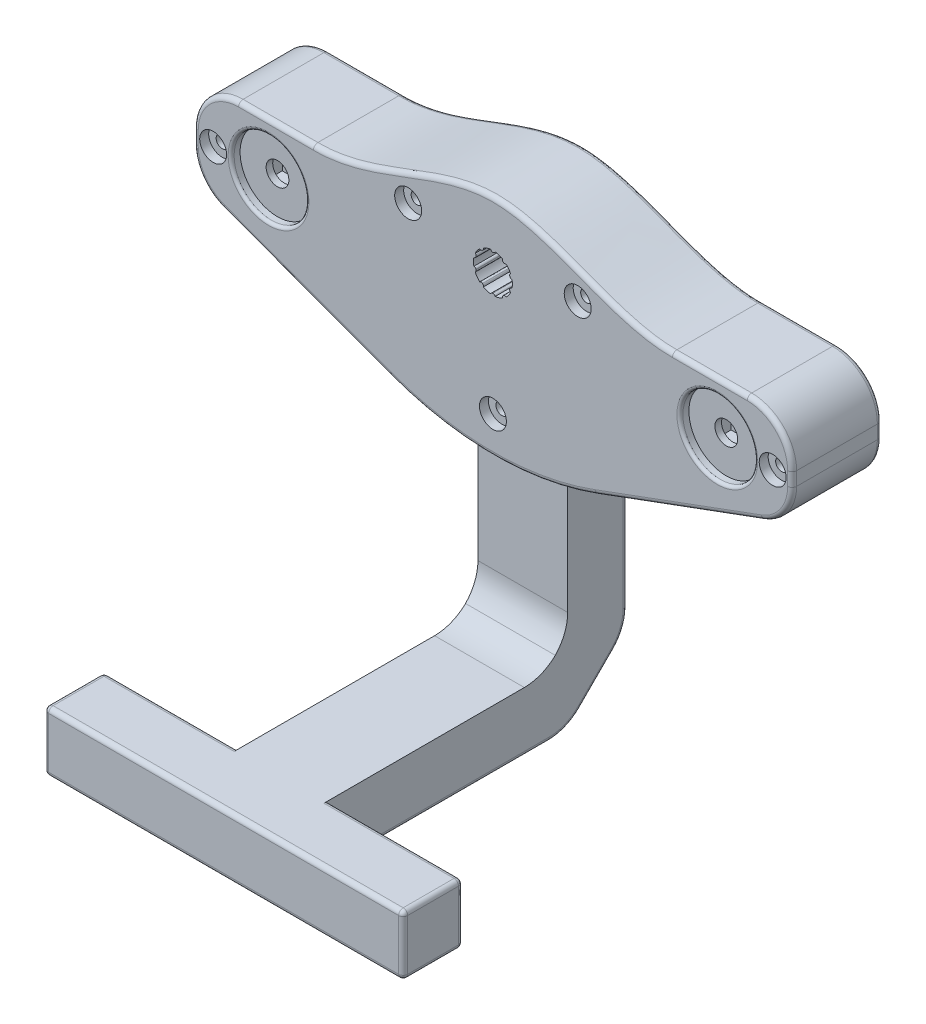
SolidWorks part; units mm, degrees
ref_plane "Front Plane" through (0, 0, 0) normal (0, 0, 1) x (1, 0, 0)
ref_plane "Top Plane" through (0, 0, 0) normal (0, 1, 0) x (1, 0, 0)
ref_plane "Right Plane" through (0, 0, 0) normal (1, 0, 0) x (0, 0, -1)
sketch "Sketch1" plane through (0, 0, 0) normal (0, 0, 1) x (1, 0, 0)
  line L0 (-100, -15) -> (0, -51.8667)
  line L2 (-100, 15) -> (-100, -15)
  line L4 (100, 15) -> (100, -15)
  line L5 (-100, 15) -> (100, -15) construction
  line L6 (-100, -15) -> (100, 15) construction
  line L7 (0, -51.8667) -> (100, -15)
  line L8 (3.1883, 2.3357) -> (2.8759, 2.7657)
  line L10 (0.75, 1.5434) -> (0.75, 2.075)
  line L11 (0.75, 2.075) -> (-0.75, 2.075)
  line L12 (-0.75, 1.5434) -> (-0.75, 2.075)
  line L13 (0, 1.5) -> (-0.75, 2.075) construction
  line L14 (0.75, 2.075) -> (0, 1.5) construction
  line L15 (4.0894, 3.6474) -> (2.8759, 2.7657)
  line L16 (4.4018, 3.2174) -> (4.0894, 3.6474)
  line L17 (5.9088, 5.2915) -> (5.4032, 5.4558)
  line L18 (5.8668, 6.8824) -> (5.4032, 5.4558)
  line L19 (6.3723, 6.7181) -> (5.8668, 6.8824)
  line L20 (6.3723, 9.2819) -> (5.8668, 9.1176)
  line L21 (5.4032, 10.5442) -> (5.8668, 9.1176)
  line L22 (5.9088, 10.7085) -> (5.4032, 10.5442)
  line L23 (4.4018, 12.7826) -> (4.0894, 12.3526)
  line L24 (2.8759, 13.2343) -> (4.0894, 12.3526)
  line L25 (3.1883, 13.6643) -> (2.8759, 13.2343)
  line L26 (0.75, 14.4566) -> (0.75, 13.925)
  line L27 (-0.75, 13.925) -> (0.75, 13.925)
  line L28 (-0.75, 14.4566) -> (-0.75, 13.925)
  line L29 (-3.1883, 13.6643) -> (-2.8759, 13.2343)
  line L30 (-4.0894, 12.3526) -> (-2.8759, 13.2343)
  line L31 (-4.4018, 12.7826) -> (-4.0894, 12.3526)
  line L32 (-5.9088, 10.7085) -> (-5.4032, 10.5442)
  line L33 (-5.8668, 9.1176) -> (-5.4032, 10.5442)
  line L34 (-6.3723, 9.2819) -> (-5.8668, 9.1176)
  line L35 (-6.3723, 6.7181) -> (-5.8668, 6.8824)
  line L36 (-5.4032, 5.4558) -> (-5.8668, 6.8824)
  line L37 (-5.9088, 5.2915) -> (-5.4032, 5.4558)
  line L38 (-4.4018, 3.2174) -> (-4.0894, 3.6474)
  line L39 (-2.8759, 2.7657) -> (-4.0894, 3.6474)
  line L40 (-3.1883, 2.3357) -> (-2.8759, 2.7657)
  line L41 (-100, 15) -> (-60, 15)
  line L42 (100, 15) -> (60, 15)
  arc A0 (0.75, 1.5434) -> (3.1883, 2.3357) centre (0, 8) ccw
  arc A1 (-3.1883, 2.3357) -> (-0.75, 1.5434) centre (0, 8) ccw
  arc A2 (-5.9088, 5.2915) -> (-4.4018, 3.2174) centre (0, 8) ccw
  arc A3 (-6.3723, 9.2819) -> (-6.3723, 6.7181) centre (0, 8) ccw
  arc A4 (-4.4018, 12.7826) -> (-5.9088, 10.7085) centre (0, 8) ccw
  arc A5 (-0.75, 14.4566) -> (-3.1883, 13.6643) centre (0, 8) ccw
  arc A6 (3.1883, 13.6643) -> (0.75, 14.4566) centre (0, 8) ccw
  arc A7 (4.4018, 3.2174) -> (5.9088, 5.2915) centre (0, 8) ccw
  arc A8 (6.3723, 6.7181) -> (6.3723, 9.2819) centre (0, 8) ccw
  arc A9 (5.9088, 10.7085) -> (4.4018, 12.7826) centre (0, 8) ccw
  spline S0 degree 3 poles (-60, 15) (-39.6994, 14.8144) (0, 45.1856) (39.6994, 14.8144) (60, 15) knots 0 0 0 0 0.5 1 1 1 1
  point P0 (0, 0)
  point P13 (0, 1.5)
  point P53 (0, 8)
  point P55 (0, 13.925)
  point P57 (0, 2.075)
  dimension "D6" = 6.5
  dimension "D2" = 40
  dimension "D3" = 40
  dimension "D4" = 30
  dimension "D5" = 30
  dimension "D7" = 11.85
  dimension "D8" = 25
  dimension "D9" = 5.5
  dimension "D10" = 5.5
  dimension "D11" = 25
  dimension "D12" = 15
  dimension "D13" = 1.5
  dimension "D14" = 22
  dimension "D1" = 10
extrude "Boss-Extrude1" add sketch "Sketch1" along normal blind 10 and the other way blind 20
sketch "Sketch18" plane through (0, 0, 0) normal (0, 0, 1) x (1, 0, 0)
  line L7 (-87.75, 12.335) -> (-62.25, 12.335)
  line L8 (-87.75, 12.335) -> (-87.75, -11.765)
  line L9 (-87.75, -11.765) -> (-62.25, -11.765)
  line L10 (-62.25, 12.335) -> (-62.25, -11.765)
  line L14 (-100, 15) -> (-60, 15) construction
  line L19 (-75, 12.335) -> (-75, -2.265) construction
  line L20 (-107.2577, -2.265) -> (-47.0612, -2.265) construction
  dimension "D1" = 24.1
  dimension "D2" = 75
  dimension "D3" = 25.5
  dimension "D6" = 14.6
  dimension "D7" = 17.265
extrude "Cut-Extrude10" cut sketch "Sketch18" along normal blind 1.1 and the other way blind 3
sketch "Sketch19" plane through (0, 0, 1.1) normal (0, 0, -1) x (-1, 0, 0)
  line L1 (70.7, 2.035) -> (79.3, 2.035)
  line L2 (70.7, 2.035) -> (70.7, -6.565)
  line L3 (70.7, -6.565) -> (79.3, -6.565)
  line L4 (79.3, 2.035) -> (79.3, -6.565)
  line L5 (70.7, 2.035) -> (79.3, -6.565) construction
  line L6 (70.7, -6.565) -> (79.3, 2.035) construction
  point P0 (75, -2.265)
  dimension "D1" = 8.6
  dimension "D2" = 8.6
sketch "Sketch20" plane through (0, 0, 1.1) normal (0, 0, -1) x (-1, 0, 0)
  line L0 (79.3, 2.035) -> (79.3, 5.335)
  line L2 (79.3, 5.335) -> (81.5, 5.335)
  line L3 (81.5, 5.335) -> (81.5, 9.835)
  line L4 (81.5, 9.835) -> (70.7, 9.835)
  line L5 (70.7, 9.835) -> (70.7, 2.035)
  line L6 (70.7, 2.035) -> (79.3, 2.035)
  line L7 (70.7, -6.565) -> (79.3, -6.565) construction
  dimension "D1" = 2.2
  dimension "D2" = 4.5
  dimension "D3" = 16.4
extrude "Cut-Extrude13" cut sketch "Sketch19" against normal blind 3.7
extrude "Cut-Extrude14" cut sketch "Sketch20" against normal blind 2
sketch "Sketch21" plane through (0, 0, 4.8) normal (0, 0, -1) x (-1, 0, 0)
  circle A0 centre (75, -2.265) radius 3.8
  dimension "D1" = 7.6
extrude "Cut-Extrude15" cut sketch "Sketch21" against normal through all
sketch "Sketch10" plane through (0, 0, 10) normal (0, 0, 1) x (1, 0, 0)
  circle A0 centre (-75, -2.265) radius 12.5
  dimension "D1" = 25
extrude "Cut-Extrude8" cut sketch "Sketch10" against normal blind 3
sketch "Sketch22" plane through (0, 0, 1.1) normal (0, 0, -1) x (-1, 0, 0)
  line L0 (62.25, -11.765) -> (62.25, 12.335) construction
  line L1 (62.25, 12.335) -> (87.75, 12.335) construction
  line L2 (87.75, 12.335) -> (87.75, -11.765) construction
  circle A0 centre (64.35, 10.235) radius 0.95
  circle A1 centre (85.65, 10.235) radius 0.95
  circle A2 centre (85.65, -2.105) radius 0.95
  circle A3 centre (64.35, -2.105) radius 0.95
  dimension "D3" = 1.9
  dimension "D6" = 1.9
  dimension "D7" = 1.9
  dimension "D9" = 1.9
  dimension "D1" = 2.1
  dimension "D2" = 2.1
  dimension "D4" = 2.1
  dimension "D5" = 2.1
  dimension "D8" = 12.34
  dimension "D10" = 2.1
  dimension "D11" = 2.1
  dimension "D12" = 12.34
extrude "Boss-Extrude5" add sketch "Sketch22" along normal blind 1.1 draft 30
ref_plane "Plane1" through (-75, 0, 0) normal (1, 0, 0) x (0, 0, -1)
sketch "Sketch24" plane through (-75, 0, 0) normal (1, 0, 0) x (0, 0, -1)
  line L0 (1.1, -11.765) -> (1.1, -19.265)
  line L1 (20, 1.5434) -> (20, 2.3357) construction
  line L3 (1.1, -19.265) -> (20, -19.265)
  line L5 (20, -19.265) -> (20, -18.665)
  line L6 (20, -18.665) -> (1.7, -18.665)
  line L8 (1.7, -18.665) -> (1.7, -11.765)
  line L9 (1.7, -11.765) -> (1.1, -11.765)
  line L12 (0, 12.335) -> (0, -11.765) construction
  point P16 (1.4, -11.765)
  dimension "D1" = 7.5
  dimension "D2" = 0.6
  dimension "D3" = 1.4
  dimension "D4" = 0.6
extrude "Cut-Extrude16" cut sketch "Sketch24" along normal mid plane 17
fillet "Fillet13" radius 2 2 edges at (-75, -18.665, -1.7) (-75, -19.265, -1.1)
sketch "Sketch25" plane through (0, 0, -3) normal (0, 0, 1) x (1, 0, 0)
  line L0 (-87.75, 12.335) -> (-87.75, -11.765) construction
  line L1 (-62.25, 12.335) -> (-87.75, 12.335) construction
  line L9 (-84.6723, 10.7392) -> (-83.3036, 10.7392)
  line L10 (-86.1542, 9.2573) -> (-86.1542, 7.8886)
  line L11 (-75, -16.0437) -> (-75, 16.0437) construction
  line L12 (-65.3277, 10.7392) -> (-66.6964, 10.7392)
  line L13 (-63.8458, 9.2573) -> (-63.8458, 7.8886)
  line L14 (-85.65, -1.005) -> (-85.65, 0.295)
  line L15 (-85.65, -3.205) -> (-85.65, -4.505)
  line L16 (-64.35, -3.205) -> (-64.35, -4.505)
  line L17 (-64.35, -1.005) -> (-64.35, 0.295)
  arc A0 (-86.1542, 9.2573) -> (-84.6723, 10.7392) centre (-85.65, 10.235) ccw
  arc A1 (-86.1542, 7.8886) -> (-83.3036, 10.7392) centre (-85.65, 10.235) ccw
  arc A4 (-85.65, -3.205) -> (-85.65, -1.005) centre (-85.65, -2.105) ccw
  arc A5 (-63.8458, 9.2573) -> (-65.3277, 10.7392) centre (-64.35, 10.235) cw
  arc A6 (-63.8458, 7.8886) -> (-66.6964, 10.7392) centre (-64.35, 10.235) cw
  arc A7 (-85.65, -4.505) -> (-85.65, 0.295) centre (-85.65, -2.105) ccw
  arc A8 (-64.35, -3.205) -> (-64.35, -1.005) centre (-64.35, -2.105) cw
  arc A9 (-64.35, -4.505) -> (-64.35, 0.295) centre (-64.35, -2.105) cw
  dimension "D3" = 2.2
  dimension "D4" = 4.8
  dimension "D6" = 2.2
  dimension "D8" = 4.8
  dimension "D1" = 2.1
  dimension "D2" = 2.1
  dimension "D5" = 2.1
  dimension "D7" = 12.34
extrude "Boss-Extrude6" add sketch "Sketch25" along normal blind 3
pattern_linear "LPattern1" count 2 spacing 150 along (1, 0, 0) of "Cut-Extrude10", "Cut-Extrude13", "Cut-Extrude14", "Cut-Extrude15", "Cut-Extrude8", "Boss-Extrude5", "Cut-Extrude16", "Fillet13", "Boss-Extrude6"
sketch "Sketch12" plane through (0, 0, -20) normal (0, 0, -1) x (-1, 0, 0)
  circle A0 centre (0, 8) radius 15
  dimension "D1" = 30
extrude "Cut-Extrude9" cut sketch "Sketch12" against normal blind 8
sketch "Sketch11" plane through (0, 0, 0) normal (0, 0, 1) x (1, 0, 0)
  line L1 (15, -46.3367) -> (-15, -46.3367)
  line L2 (15, -46.3367) -> (15, -102.265)
  line L3 (15, -102.265) -> (-15, -102.265)
  line L4 (-15, -46.3367) -> (-15, -102.265)
  line L7 (-100, -15) -> (0, -51.8667) construction
  circle A0 centre (-75, -2.265) radius 3.8 construction
  point P9 (0, -46.3367)
  dimension "D1" = 100
  dimension "D2" = 30
extrude "Boss-Extrude2" add sketch "Sketch11" against normal blind 20
sketch "Sketch16" plane through (0, 0, 0) normal (1, 0, 0) x (0, 0, -1)
  line L0 (20, -102.265) -> (0, -122.265)
  line L1 (20, -102.265) -> (20, -46.3367) construction
  line L2 (0, -122.265) -> (-100, -122.265)
  line L3 (-100, -122.265) -> (-100, -102.265)
  line L6 (-100, -102.265) -> (-8.2843, -102.265)
  line L7 (-8.2843, -102.265) -> (0, -93.9807)
  line L8 (0, -93.9807) -> (20, -102.265)
  line L10 (0, -46.3367) -> (0, -51.8667) construction
  dimension "D1" = 100
  dimension "D2" = 20
  dimension "D3" = 20
  dimension "D4" = 135
  dimension "D5" = 100
extrude "Boss-Extrude3" add sketch "Sketch16" along normal mid plane 30
sketch "Sketch17" plane through (0, -122.265, 0) normal (0, -1, 0) x (1, 0, 0)
  line L0 (15, 100) -> (-15, 100) construction
  line L1 (-60, 100) -> (60, 100)
  line L2 (-60, 100) -> (-60, 80)
  line L3 (-60, 80) -> (60, 80)
  line L4 (60, 100) -> (60, 80)
  point P4 (0, 100)
  dimension "D1" = 20
  dimension "D2" = 120
extrude "Boss-Extrude4" add sketch "Sketch17" against normal blind 20
chamfer "Chamfer1" distance 1.5 distance2 0.4624 10 edges at (-5.635, 6.1691, -12) (-3.4826, 3.2066, -12) (0, 2.075, -12) (3.4826, 3.2066, -12) (5.635, 6.1691, -12) (5.635, 9.8309, -12) (-5.635, 9.8309, -12) (-3.4826, 12.7934, -12) (0, 13.925, -12) (3.4826, 12.7934, -12)
chamfer "Chamfer2" distance 5 distance2 8 1 edges at (-15, 8, -20)
fillet "Fillet11" radius 0.78 20 edges at (-4.0894, 12.3526, -0.25) (-5.8668, 9.1176, -0.25) (-5.4032, 10.5442, -0.25) (-2.8759, 13.2343, -0.25) (-0.75, 13.925, -0.25) (0.75, 13.925, -0.25) (2.8759, 13.2343, -0.25) (4.0894, 12.3526, -0.25) (5.4032, 10.5442, -0.25) (5.8668, 9.1176, -0.25) (5.8668, 6.8824, -0.25) (5.4032, 5.4558, -0.25) (-5.8668, 6.8824, -0.25) (-5.4032, 5.4558, -0.25) (-4.0894, 3.6474, -0.25) (-2.8759, 2.7657, -0.25) (-0.75, 2.075, -0.25) (0.75, 2.075, -0.25) (2.8759, 2.7657, -0.25) (4.0894, 3.6474, -0.25)
fillet "Fillet1" radius 15 8 edges at (100, -15, -5) (-100, -15, -5) (0, -122.265, 0) (0, -102.265, -20) (0, -102.265, 8.2843) (0, -93.9807, 0) (100, 15, -5) (-100, 15, -5)
fillet "Fillet12" radius 100 1 edges at (0, -51.8667, 5)
fillet "Fillet2" radius 1.5 51 edges at (100, -2.2716, -20) (100, -2.2716, 10) (97.3051, -13.1213, -20) (97.3051, -13.1213, 10) (62.3897, -28.8657, 10) (62.3897, -28.8657, -20) (-62.3897, -28.8657, -20) (-62.3897, -28.8657, 10) (-97.3051, -13.1213, -20) (-97.3051, -13.1213, 10) (-100, -2.2716, 10) (-100, -2.2716, -20) (15, -70.1039, -20) (-15, -70.1039, -20) (15, -122.265, 43.1066) (15, -112.265, -10) (-15, -122.265, 43.1066) (-15, -112.265, -10) (15, -121.1232, 0.473) (15, -101.792, -18.8582) (-15, -121.1232, 0.473) (-15, -101.792, -18.8582) (72.5, 15, 10) (72.5, 15, -20) (95.6066, 10.6066, -20) (95.6066, 10.6066, 10) (-72.5, 15, -20) (-72.5, 15, 10) (-95.6066, 10.6066, -20) (-95.6066, 10.6066, 10) (37.5, -122.265, 80) (60, -122.265, 90) (0, -122.265, 100) (-60, -122.265, 90) (-37.5, -122.265, 80) (-60, -112.265, 80) (-60, -102.265, 90) (60, -102.265, 90) (60, -112.265, 80) (60, -112.265, 100) (-60, -112.265, 100) (0, -102.265, 100) (-37.5, -102.265, 80) (37.5, -102.265, 80) (24.9232, -42.1317, -20) (-24.9232, -42.1317, -20) (0, -45.2873, 10) (-15, -44.1559, -10) (15, -44.1559, -10)
fillet "Fillet14" radius 1 3 edges at (-62.5, -2.265, 10) (87.5, -2.265, 10) (-20, 8, -20)
sketch "Sketch32" plane through (0, 0, 10) normal (0, 0, 1) x (1, 0, 0)
  line L0 (-98.5, 0) -> (-98.5, -4.5431) construction
  line L1 (0, -70.9875) -> (0, 70.9875) construction
  circle A0 centre (-93.5, -2.2716) radius 4.5
  circle A2 centre (-28.3322, 14.0083) radius 4.5
  circle A3 centre (0, -32.7928) radius 4.5
  circle A7 centre (28.3322, 14.0083) radius 4.5
  circle A9 centre (93.5, -2.2716) radius 4.5
  point P6 (-98.5, -2.2716)
  dimension "D1" = 9
  dimension "D3" = 9
  dimension "D4" = 9
  dimension "D2" = 5
sketch "Sketch33" plane through (0, 0, 10) normal (0, 0, 1) x (1, 0, 0)
  circle A0 centre (-28.3322, 14.0083) radius 2
  circle A1 centre (-93.5, -2.2716) radius 2
  circle A2 centre (0, -32.7928) radius 2
  circle A3 centre (28.3322, 14.0083) radius 2
  circle A4 centre (93.5, -2.2716) radius 2
extrude "Cut-Extrude17" cut sketch "Sketch32" against normal blind 3
extrude "Cut-Extrude18" cut sketch "Sketch33" against normal through all
sketch "Sketch35" plane through (0, 0, -20) normal (0, 0, -1) x (-1, 0, 0)
  line L1 (-98.05, 0.3554) -> (-98.05, -4.8985)
  line L2 (-98.05, -4.8985) -> (-93.5, -7.5254)
  line L3 (-93.5, -7.5254) -> (-88.95, -4.8985)
  line L4 (-88.95, -4.8985) -> (-88.95, 0.3554)
  line L5 (-88.95, 0.3554) -> (-93.5, 2.9823)
  line L6 (-93.5, 2.9823) -> (-98.05, 0.3554)
  line L7 (4.55, -30.1659) -> (0, -27.539)
  line L8 (0, -27.539) -> (-4.55, -30.1659)
  line L9 (-4.55, -30.1659) -> (-4.55, -35.4198)
  line L10 (-4.55, -35.4198) -> (0, -38.0467)
  line L11 (0, -38.0467) -> (4.55, -35.4198)
  line L12 (4.55, -35.4198) -> (4.55, -30.1659)
  line L13 (-23.7822, 16.6353) -> (-28.3322, 19.2622)
  line L14 (-28.3322, 19.2622) -> (-32.8822, 16.6353)
  line L15 (-32.8822, 16.6353) -> (-32.8822, 11.3814)
  line L16 (-32.8822, 11.3814) -> (-28.3322, 8.7545)
  line L17 (-28.3322, 8.7545) -> (-23.7822, 11.3814)
  line L18 (-23.7822, 11.3814) -> (-23.7822, 16.6353)
  line L19 (32.8822, 16.6353) -> (28.3322, 19.2622)
  line L20 (28.3322, 19.2622) -> (23.7822, 16.6353)
  line L21 (23.7822, 16.6353) -> (23.7822, 11.3814)
  line L22 (23.7822, 11.3814) -> (28.3322, 8.7545)
  line L23 (28.3322, 8.7545) -> (32.8822, 11.3814)
  line L24 (32.8822, 11.3814) -> (32.8822, 16.6353)
  line L25 (98.05, 0.3554) -> (93.5, 2.9823)
  line L26 (93.5, 2.9823) -> (88.95, 0.3554)
  line L27 (88.95, 0.3554) -> (88.95, -4.8985)
  line L28 (88.95, -4.8985) -> (93.5, -7.5254)
  line L29 (93.5, -7.5254) -> (98.05, -4.8985)
  line L30 (98.05, -4.8985) -> (98.05, 0.3554)
  circle A0 centre (-93.5, -2.2716) radius 4.55 construction
  circle A1 centre (0, -32.7928) radius 4.55 construction
  circle A2 centre (-28.3322, 14.0083) radius 4.55 construction
  circle A3 centre (28.3322, 14.0083) radius 4.55 construction
  circle A4 centre (93.5, -2.2716) radius 4.55 construction
extrude "Cut-Extrude19" cut sketch "Sketch35" against normal blind 5
split "Split2" [suppressed] bodies to split 133
